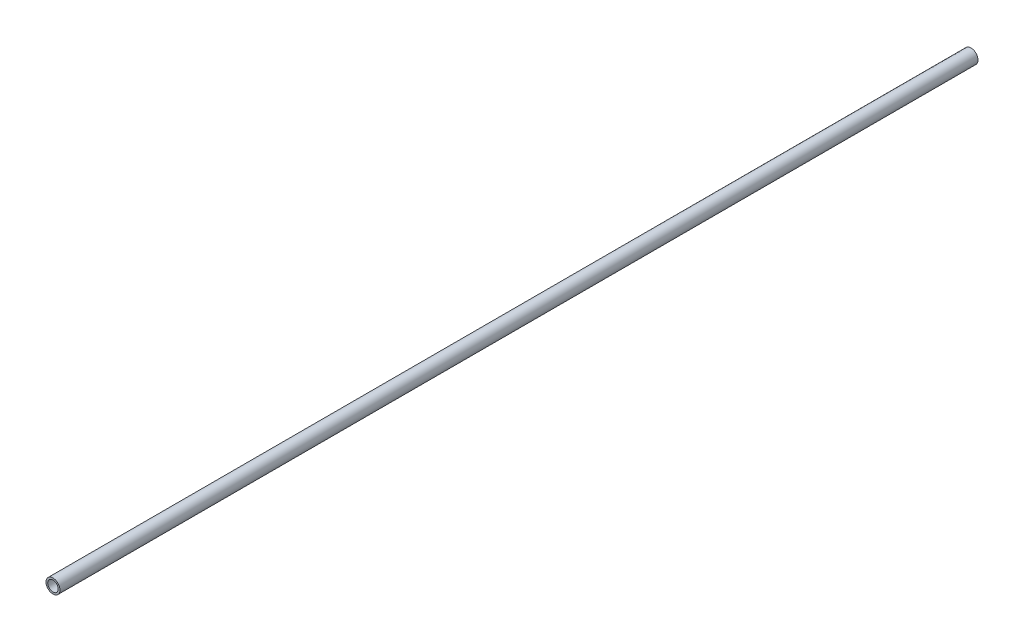
SolidWorks part; units mm, degrees
material "FR-4"
ref_plane "Front Plane" through (0, 0, 0) normal (0, 0, 1) x (1, 0, 0)
ref_plane "Top Plane" through (0, 0, 0) normal (0, 1, 0) x (1, 0, 0)
ref_plane "Right Plane" through (0, 0, 0) normal (1, 0, 0) x (0, 0, -1)
ref_axis "Centre Axis" through (0, 0, -232.2463) along (0, 0, 1)
sketch "Sketch1" plane through (0, 0, 0) normal (0, 0, 1) x (1, 0, 0)
  circle A0 centre (0, 0) radius 3.175
  circle A1 centre (0, 0) radius 2.3812
  dimension "D1" = 6.35
  dimension "D2" = 0.7937
extrude "Boss-Extrude1" add sketch "Sketch1" along normal mid plane 417.6
